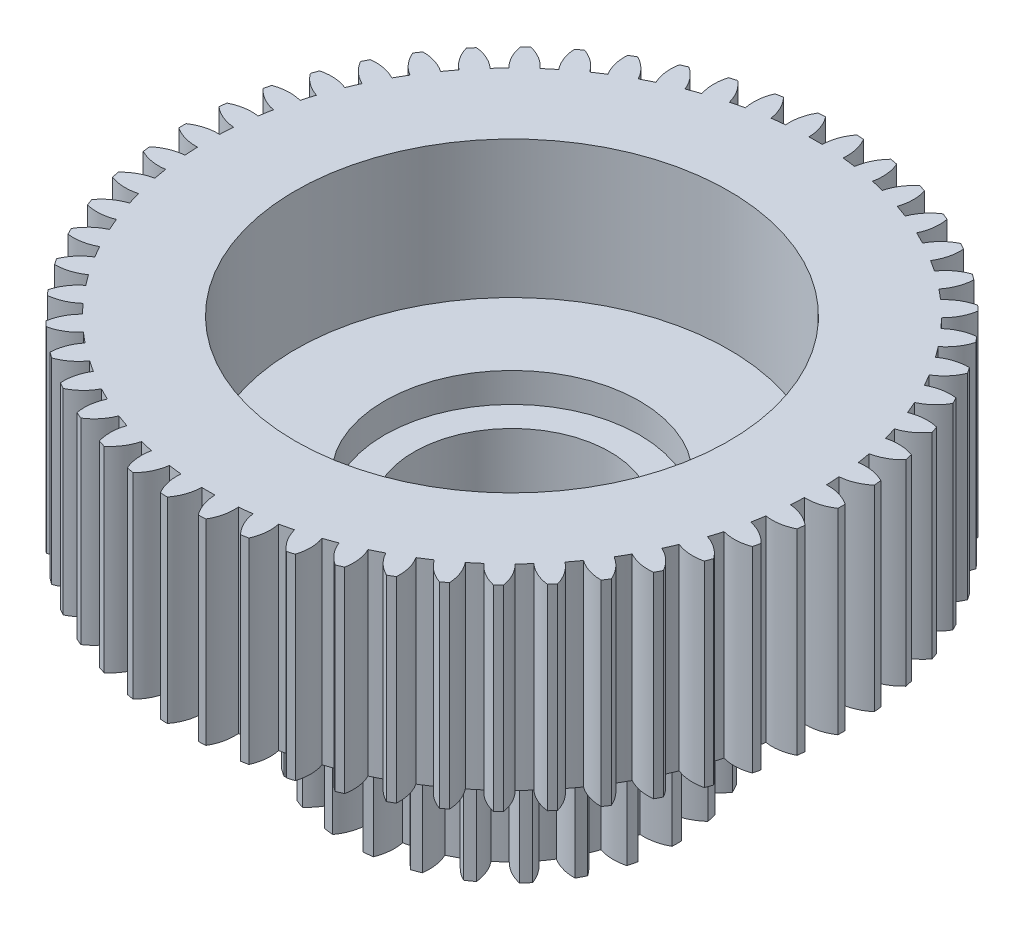
SolidWorks part; units mm, degrees
ref_plane "Ebene vorne" through (0, 0, 0) normal (0, 0, 1) x (1, 0, 0)
ref_plane "Ebene oben" through (0, 0, 0) normal (0, 1, 0) x (1, 0, 0)
ref_plane "Ebene rechts" through (0, 0, 0) normal (1, 0, 0) x (0, 0, -1)
sketch "Skizze1" plane through (0, 0, 0) normal (0, 1, 0) x (1, 0, 0)
  circle A0 centre (0, 0) radius 8.4
  circle A1 centre (0, 0) radius 5
  dimension "D2" = 10
  dimension "D1" = 16.8
extrude "Aufsatz-Linear austragen1" add sketch "Skizze1" along normal blind 9.1
sketch "Skizze2" plane through (0, 9.1, 0) normal (0, 1, 0) x (1, 0, 0)
  circle A0 centre (0, 0) radius 16.8
  circle A1 centre (0, 0) radius 5
  dimension "D1" = 33.6
  dimension "D2" = 10
extrude "Aufsatz-Linear austragen2" add sketch "Skizze2" along normal blind 10
sketch "Skizze3" plane through (0, 19.1, 0) normal (0, 1, 0) x (1, 0, 0)
  circle A0 centre (0, 0) radius 11.05
  dimension "D1" = 22.1
extrude "Schnitt-Linear austragen1" cut sketch "Skizze3" against normal blind 7
sketch "Skizze5" plane through (0, 19.1, 0) normal (0, 1, 0) x (1, 0, 0)
  line L0 (0, 0) -> (0, 16.8) construction
  line L1 (0, 0) -> (-0.3367, 15.4763) construction
  line L2 (0, 0) -> (0.9768, 16.7716) construction
  line L3 (-0.4712, 16.1931) -> (0.4712, 16.1931) construction
  line L4 (0.4712, 16.1931) -> (1.4119, 16.1384) construction
  line L5 (0, 14.8986) -> (-0.6869, 16.786) construction
  circle A0 centre (0, 0) radius 16.8
  circle A1 centre (0, 0) radius 16.2 construction
  circle A2 centre (0, 0) radius 15.48
  arc A3 (-0.792, 16.7813) -> (-0.3367, 15.4763) centre (-2.5744, 15.4277) cw
  arc A4 (0.792, 16.7813) -> (0.3367, 15.4763) centre (2.5744, 15.4277) ccw
  dimension "D1" = 33.6
  dimension "D2" = 32.4
  dimension "D3" = 30.96
  dimension "D4" = 3.333
  dimension "D5" = 20
extrude "Schnitt-Linear austragen2" cut sketch "Skizze5" against normal up to surface (10 mm away) contours A4 A0 A3 A2 region at (0, 19.1, -16.2378) up to face at (0, 9.1, 8.4)
pattern_circular "Kreismuster1" count 54 over 360 about axis through (0, 12.1, 0) along (0, 1, 0) of "Schnitt-Linear austragen2"
sketch "Skizze6" plane through (0, 0, 0) normal (0, -1, 0) x (1, 0, 0)
  line L0 (0, 0) -> (0, 8.4) construction
  line L1 (0, 0) -> (-0.328, 7.0724) construction
  line L2 (0, 0) -> (1.0125, 8.3388) construction
  line L3 (-0.471, 7.7858) -> (0.471, 7.7858) construction
  line L4 (0.471, 7.7858) -> (1.406, 7.6722) construction
  line L5 (0, 6.4918) -> (-0.6844, 8.3721) construction
  circle A0 centre (0, 0) radius 8.4
  circle A1 centre (0, 0) radius 7.8 construction
  circle A2 centre (0, 0) radius 7.08
  arc A3 (-0.7757, 8.3641) -> (-0.328, 7.0724) centre (-2.7381, 6.9606) cw
  arc A4 (0.7757, 8.3641) -> (0.328, 7.0724) centre (2.7381, 6.9606) ccw
  dimension "D1" = 16.8
  dimension "D5" = 20
  dimension "D2" = 15.6
  dimension "D3" = 14.16
  dimension "D4" = 6.923
extrude "Schnitt-Linear austragen3" cut sketch "Skizze6" against normal up to surface (9.1 mm away) contours A4 A0 A3 A2 region at (0, 0, 7.8346) up to face at (0, 9.1, 8.4)
pattern_circular "Kreismuster2" count 26 over 360 about axis through (0, 9.1, 0) along (0, -1, 0) of "Schnitt-Linear austragen3" reverse direction yes
sketch "Skizze7" plane through (0, 12.1, 0) normal (0, 1, 0) x (1, 0, 0)
  circle A0 centre (0, 0) radius 6.5
  dimension "D1" = 13
extrude "Schnitt-Linear austragen4" cut sketch "Skizze7" against normal blind 1.5
equation "\"Tooth1\"= 54"
equation "\"Tooth2\"= 26"
equation "\"Module\"= 0.6mm"
equation "\"D1@Skizze2\"=(\"Tooth1\"+2)*\"Module\""
equation "\"D1@Skizze1\"=(\"Tooth2\"+2)*\"Module\""
equation "\"D1@Skizze5\"=(\"Tooth1\"+2)*\"Module\""
equation "\"D2@Skizze5\"=\"Tooth1\"*\"Module\""
equation "\"D3@Skizze5\"=(\"Module\"*\"Tooth1\"- (\"Module\"*if(\"Module\" => 1.25,2.25,2.4)))"
equation "\"D4@Skizze5\"=180/\"Tooth1\""
equation "\"D1@Kreismuster1\"=\"Tooth1\""
equation "\"D3@Skizze6\"=(\"Module\"*\"Tooth2\"- (\"Module\"*if(\"Module\" => 1.25,2.25,2.4)))"
equation "\"D2@Skizze6\"=\"Tooth2\"*\"Module\""
equation "\"D1@Skizze6\"=(\"Tooth2\"+2)*\"Module\""
equation "\"D4@Skizze6\"=180/\"Tooth2\""
equation "\"D1@Kreismuster2\"=\"Tooth2\""
